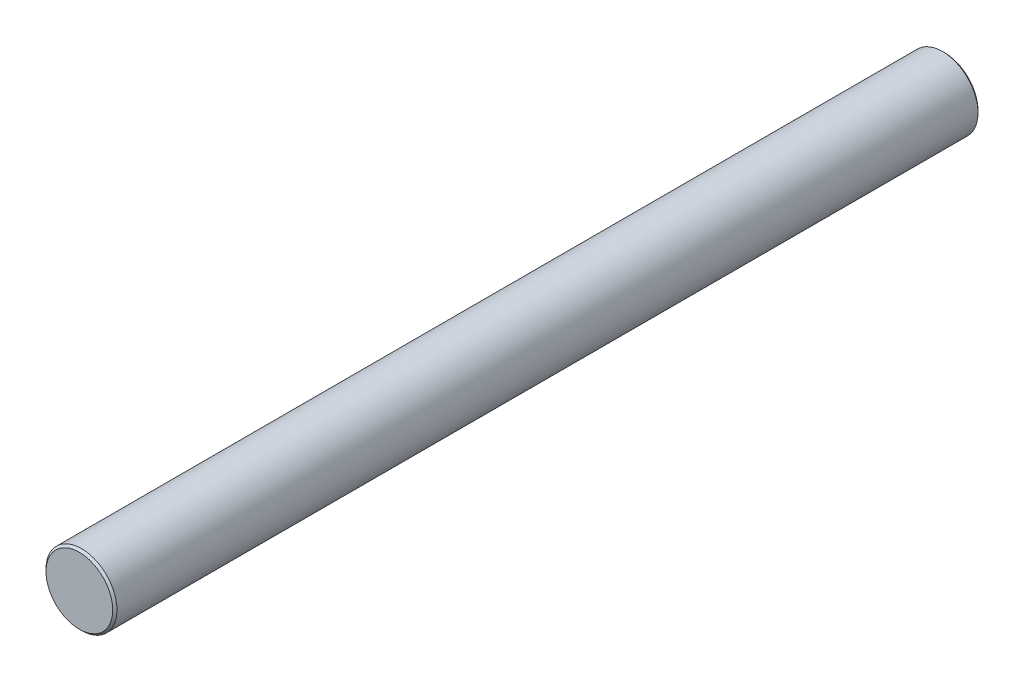
SolidWorks part; units mm, degrees
material "Alloy Steel"
ref_plane "Front Plane" through (0, 0, 0) normal (0, 0, 1) x (1, 0, 0)
ref_plane "Top Plane" through (0, 0, 0) normal (0, 1, 0) x (1, 0, 0)
ref_plane "Right Plane" through (0, 0, 0) normal (1, 0, 0) x (0, 0, -1)
sketch "Sketch1" plane through (0, 0, 0) normal (1, 0, 0) x (0, 0, -1)
  line L0 (152.4, 0) -> (-152.4, 0) construction
  line L1 (-152.4, -12.5) -> (-152.4, 12.5) construction
  point P4 (0, 0)
  point P8 (-152.4, 0)
  dimension "Length" = 304.8
  dimension "Diameter" = 25
sketch "Sketch2" plane through (0, 0, 0) normal (1, 0, 0) x (0, 0, -1)
  line L0 (-152.4, 0) -> (-152.4, 12.5)
  line L1 (-152.4, 12.5) -> (152.4, 12.5)
  line L2 (152.4, 12.5) -> (152.4, 0)
  line L3 (152.4, 0) -> (-152.4, 0)
revolve "Revolve1" add sketch "Sketch2" angle 360 about L3
chamfer "Chamfer1" distance 0.75 angle 45 2 edges at (0, 12.5, -152.4) (0, 12.5, 152.4)
sketch "Sketch3" plane through (0, 0, 0) normal (1, 0, 0) x (0, 0, -1)
  line L0 (152.4, 0) -> (-152.4, 0) construction
  line L1 (-152.4, 12.5) -> (152.4, 12.5) construction
  point P0 (-123.65, 0)
  point P1 (123.65, 0)
  point P4 (-114.0667, 0)
  point P5 (119.2024, 0)
  point P6 (-152.4, 12.5)
  point P13 (152.4, 12.5)
  dimension "Length" = 304.8
  dimension "D1" = 28.75
  dimension "D2" = 28.75
  dimension "D3" = 38.3333
  dimension "D4" = 33.1976
sketch "Sketch4" plane through (0, 0, 0) normal (0, 0, 1) x (1, 0, 0)
  line L0 (12.5, 0) -> (-12.5, 0) construction
  point P4 (0, 0)
  dimension "Diameter" = 25
equation "\"D1@Chamfer1\"=\"Diameter@Sketch1\"*.03"
equation "\"D1@Sketch3\"=\"Diameter@Sketch1\"*1.15"
equation "\"D2@Sketch3\"=\"D1@Sketch3\""
equation "\"D3@Sketch3\"=\"D1@Sketch3\"*(4/3)"
equation "\"D4@Sketch3\"=(\"D1@Sketch3\")/(TAN(0.5236rad)*2)*4/3"
equation "\"Diameter@Sketch4\" = \"Diameter@Sketch1\""
equation "\"Length@Sketch3\"=\"Length@Sketch1\""
